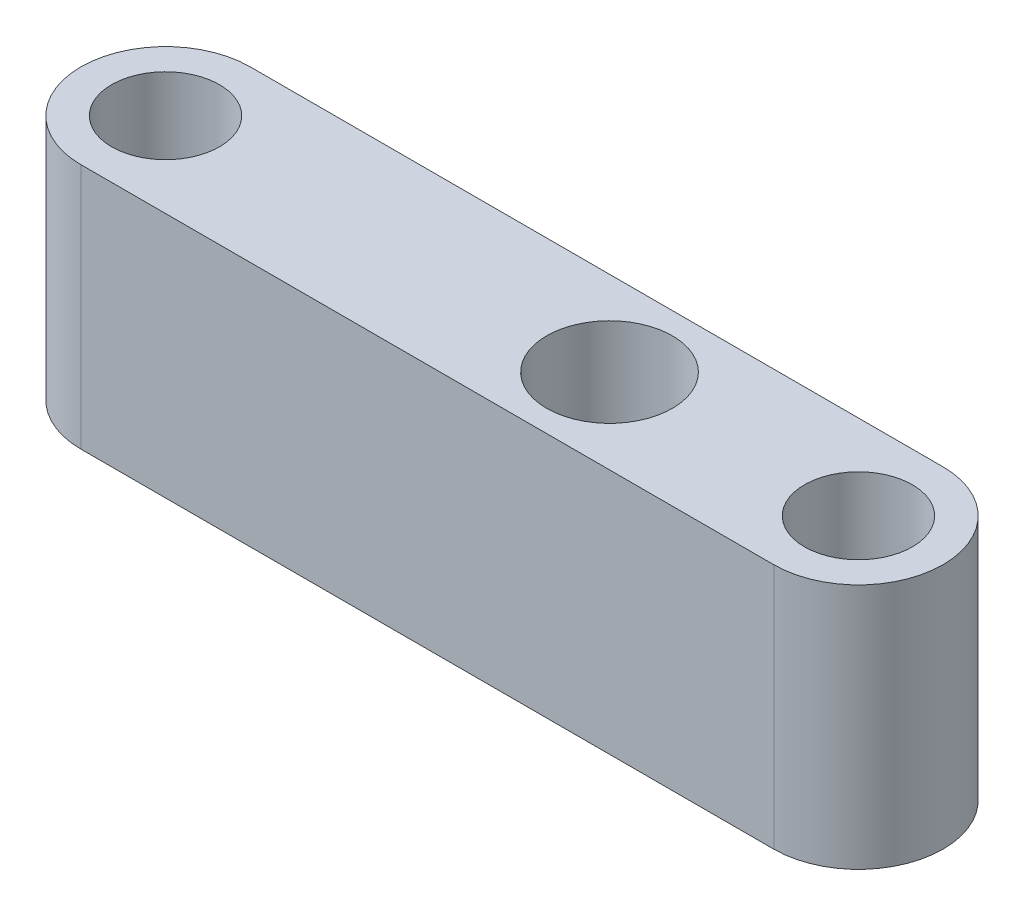
SolidWorks part; units mm, degrees
ref_plane "Front Plane" through (0, 0, 0) normal (0, 0, 1) x (1, 0, 0)
ref_plane "Top Plane" through (0, 0, 0) normal (0, 1, 0) x (1, 0, 0)
ref_plane "Right Plane" through (0, 0, 0) normal (1, 0, 0) x (0, 0, -1)
sketch "Sketch1" plane through (0, 0, 0) normal (0, 1, 0) x (1, 0, 0)
  line L0 (0, 0) -> (50000, 0) construction
  line L1 (16.8, -3.3) -> (-16.8, -3.3) construction
  line L2 (16.8, -3.3) -> (16.8, 3.3) construction
  line L3 (16.8, 3.3) -> (-16.8, 3.3) construction
  line L4 (-16.8, -3.3) -> (-16.8, 3.3) construction
  line L5 (16.8, -3.3) -> (-16.8, 3.3) construction
  line L6 (16.8, 3.3) -> (-16.8, -3.3) construction
  line L7 (0, 0) -> (0, 50000) construction
  line L8 (-13.5, -3.3) -> (13.5, -3.3)
  line L9 (-13.5, 3.3) -> (13.5, 3.3)
  circle A0 centre (13.5, 0) radius 3.3 construction
  circle A1 centre (-13.5, 0) radius 3.3 construction
  arc A2 (-13.5, 3.3) -> (-13.5, -3.3) centre (-13.5, 0) ccw
  arc A3 (13.5, 3.3) -> (13.5, -3.3) centre (13.5, 0) cw
  point P0 (0, 0)
  dimension "D1" = 6.6
  dimension "D2" = 33.6
extrude "Boss-Extrude1" add sketch "Sketch1" along normal blind 9.6 contours A3 L9 A2 L8 region at (0, 0, 0)
sketch "Sketch2" plane through (0, 9.6, 0) normal (0, 1, 0) x (1, 0, 0)
  circle A0 centre (-13.5, 0) radius 2.1
  arc A1 (-13.5, 3.3) -> (-13.5, -3.3) centre (-13.5, 0) ccw construction
  point P5 (-16.8, 0)
  dimension "D1" = 3.3
  dimension "4.2" = 4.2
extrude "Cut-Extrude1" cut sketch "Sketch2" against normal through all
mirror "Mirror1" about plane through (0, 0, 0) normal (1, 0, 0) of "Cut-Extrude1"
sketch "Sketch3" plane through (0, 9.6, 0) normal (0, 1, 0) x (1, 0, 0)
  line L2 (0, 0) -> (-50000, 0) construction
  circle A0 centre (3.8, 0) radius 2.45
  arc A1 (13.5, -3.3) -> (13.5, 3.3) centre (13.5, 0) ccw construction
  point P5 (16.8, 0)
  point P8 (3.8194, 0.7101)
  point P9 (0, 0)
  dimension "D1" = 4.9
  dimension "D2" = 13
extrude "Cut-Extrude2" cut sketch "Sketch3" against normal through all
